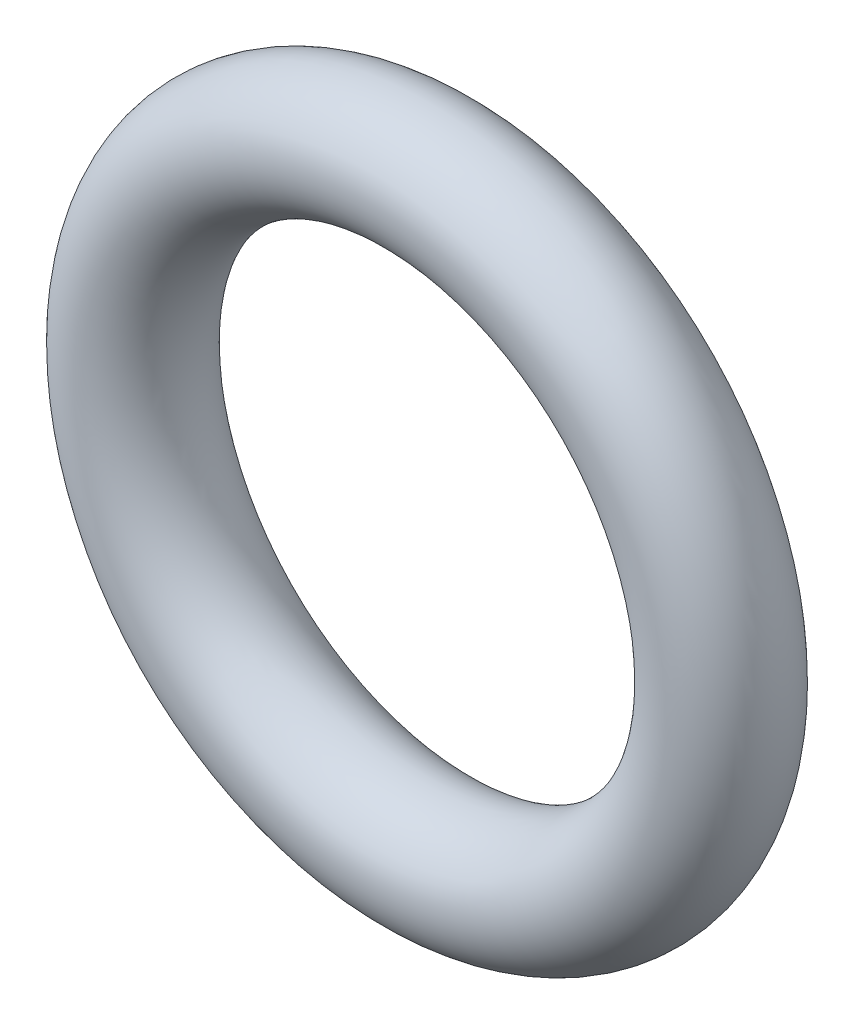
SolidWorks part; units mm, degrees
ref_plane "Front" through (0, 0, 0) normal (0, 0, 1) x (1, 0, 0)
ref_plane "Top" through (0, 0, 0) normal (0, 1, 0) x (1, 0, 0)
ref_plane "Right" through (0, 0, 0) normal (1, 0, 0) x (0, 0, -1)
sketch "Sketch1" plane through (0, 0, 0) normal (0, 0, 1) x (1, 0, 0)
  circle A0 centre (0, 0) radius 3.05
  dimension "d1" = 6.1
sketch "Sketch2" plane through (0, 0, 0) normal (0, 1, 0) x (1, 0, 0)
  circle A0 centre (-3.85, 0) radius 0.8
  point P2 (-3.05, 0)
  dimension "d2" = 1.6
sweep "Sweep1" add profiles "Sketch2" path "Sketch1"
ref_axis "Axis1" through (0, 0, -2.9751) along (0, 0, 1)
